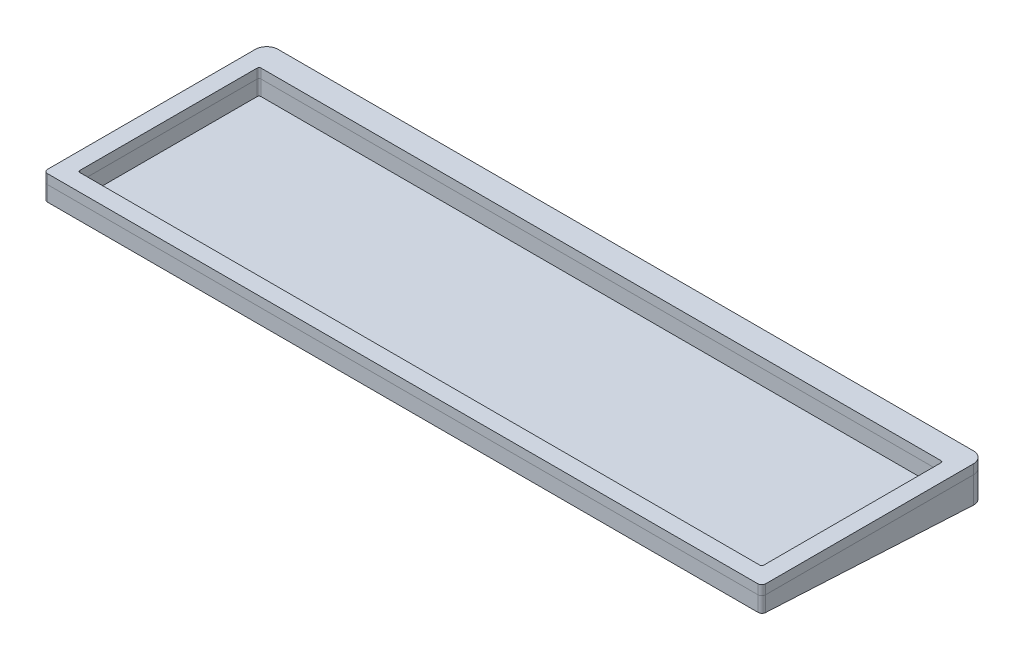
SolidWorks part; units mm, degrees
ref_plane "Front Plane" through (0, 0, 0) normal (0, 0, 1) x (1, 0, 0)
ref_plane "Top Plane" through (0, 0, 0) normal (0, 1, 0) x (1, 0, 0)
ref_plane "Right Plane" through (0, 0, 0) normal (1, 0, 0) x (0, 0, -1)
sketch "Sketch1" plane through (0, 0, 0) normal (0, 1, 0) x (1, 0, 0)
  line L1 (-178.825, 47.625) -> (178.825, 47.625)
  line L2 (-179.825, 46.625) -> (-179.825, -46.625)
  line L3 (-178.825, -47.625) -> (178.825, -47.625)
  line L4 (179.825, 46.625) -> (179.825, -46.625)
  line L5 (-179.825, 47.625) -> (179.825, -47.625) construction
  line L6 (-179.825, -47.625) -> (179.825, 47.625) construction
  arc A0 (178.825, -47.625) -> (179.825, -46.625) centre (178.825, -46.625) ccw
  arc A1 (178.825, 47.625) -> (179.825, 46.625) centre (178.825, 46.625) cw
  arc A2 (-179.825, -46.625) -> (-178.825, -47.625) centre (-178.825, -46.625) ccw
  arc A3 (-178.825, 47.625) -> (-179.825, 46.625) centre (-178.825, 46.625) ccw
  circle A4 centre (157.075, 19.175) radius 1.1
  circle A5 centre (136.925, -16.775) radius 1.1
  circle A6 centre (-153.475, 33.725) radius 1.1
  circle A7 centre (17.925, 22.275) radius 1.1
  circle A8 centre (17.875, -35.075) radius 1.1
  circle A9 centre (-130.375, -35.725) radius 1.1
  point P0 (0, 0)
  dimension "D3" = 1
  dimension "D4" = 2.2
  dimension "D7" = 2.2
  dimension "D8" = 2.2
  dimension "D9" = 2.2
  dimension "D10" = 2.2
  dimension "D11" = 2.2
  dimension "D1" = 359.65
  dimension "D2" = 95.25
  dimension "D5" = 22.75
  dimension "D6" = 28.45
  dimension "D12" = 42.9
  dimension "D13" = 30.85
  dimension "D14" = 25.35
  dimension "D15" = 161.9
  dimension "D16" = 12.55
  dimension "D17" = 161.95
  dimension "D18" = 11.9
  dimension "D19" = 49.45
  dimension "D20" = 13.9
  dimension "D21" = 26.35
sketch "Sketch2" plane through (0, 0, 0) normal (0, 1, 0) x (1, 0, 0)
  line L0 (-179.825, 46.625) -> (-179.825, -46.625) construction
  line L1 (-178.825, -47.625) -> (178.825, -47.625) construction
  line L2 (179.825, 46.625) -> (179.825, -46.625) construction
  line L3 (-178.825, 47.625) -> (178.825, 47.625) construction
  line L4 (-179.825, 46.625) -> (-179.825, -46.625)
  line L5 (-178.825, -47.625) -> (178.825, -47.625)
  line L6 (179.825, 46.625) -> (179.825, -46.625)
  line L7 (-178.825, 47.625) -> (178.825, 47.625)
  line L9 (-182.825, 60.625) -> (182.825, 60.625)
  line L10 (-188.825, 54.625) -> (-188.825, -54.625)
  line L11 (-186.825, -56.625) -> (186.825, -56.625)
  line L12 (188.825, 54.625) -> (188.825, -54.625)
  circle A0 centre (157.075, 19.175) radius 1.1 construction
  circle A1 centre (136.925, -16.775) radius 1.1 construction
  circle A2 centre (17.875, -35.075) radius 1.1 construction
  circle A3 centre (17.925, 22.275) radius 1.1 construction
  circle A4 centre (-153.475, 33.725) radius 1.1 construction
  circle A5 centre (-130.375, -35.725) radius 1.1 construction
  arc A6 (-179.825, -46.625) -> (-178.825, -47.625) centre (-178.825, -46.625) ccw construction
  arc A7 (178.825, -47.625) -> (179.825, -46.625) centre (178.825, -46.625) ccw construction
  arc A8 (179.825, 46.625) -> (178.825, 47.625) centre (178.825, 46.625) ccw construction
  arc A9 (-178.825, 47.625) -> (-179.825, 46.625) centre (-178.825, 46.625) ccw construction
  circle A10 centre (157.075, 19.175) radius 1.1
  circle A11 centre (136.925, -16.775) radius 1.1
  circle A12 centre (17.875, -35.075) radius 1.1
  circle A13 centre (17.925, 22.275) radius 1.1
  circle A14 centre (-153.475, 33.725) radius 1.1
  circle A15 centre (-130.375, -35.725) radius 1.1
  arc A16 (-179.825, -46.625) -> (-178.825, -47.625) centre (-178.825, -46.625) ccw
  arc A17 (178.825, -47.625) -> (179.825, -46.625) centre (178.825, -46.625) ccw
  arc A18 (179.825, 46.625) -> (178.825, 47.625) centre (178.825, 46.625) ccw
  arc A19 (-178.825, 47.625) -> (-179.825, 46.625) centre (-178.825, 46.625) ccw
  arc A20 (182.825, 60.625) -> (188.825, 54.625) centre (182.825, 54.625) cw
  arc A21 (-182.825, 60.625) -> (-188.825, 54.625) centre (-182.825, 54.625) ccw
  arc A22 (186.825, -56.625) -> (188.825, -54.625) centre (186.825, -54.625) ccw
  arc A23 (-188.825, -54.625) -> (-186.825, -56.625) centre (-186.825, -54.625) ccw
  point P30 (0, 0)
  dimension "D5" = 6
  dimension "D6" = 2
  dimension "D1" = 13
  dimension "D2" = 9
  dimension "D3" = 9
  dimension "D4" = 9
extrude "Boss-Extrude1" add sketch "Sketch2" along normal blind 13 contours L10 A23 L11 A22 L12 A20 L9 A21 A19 L7 A18 L6 A17 L5 A16 L4 region at (0, 0, -56.6707)
sketch "Sketch4" plane through (0, 0, 0) normal (0, -1, 0) x (1, 0, 0)
  line L0 (188.825, -54.625) -> (188.825, 54.625) construction
  line L1 (-182.825, -60.625) -> (182.825, -60.625) construction
  line L2 (-188.825, -54.625) -> (-188.825, 54.625) construction
  line L3 (-186.825, 56.625) -> (186.825, 56.625) construction
  line L4 (-179.825, 46.625) -> (-179.825, -46.625)
  line L5 (178.825, 47.625) -> (-178.825, 47.625)
  line L6 (179.825, -46.625) -> (179.825, 46.625)
  line L7 (-178.825, -47.625) -> (178.825, -47.625)
  line L8 (-179.825, 46.625) -> (-179.825, -46.625)
  line L10 (179.825, -46.625) -> (179.825, 46.625)
  line L11 (-178.825, -47.625) -> (178.825, -47.625)
  line L12 (188.825, -54.625) -> (188.825, 54.625)
  line L13 (-182.825, -60.625) -> (182.825, -60.625)
  line L14 (-188.825, -54.625) -> (-188.825, 54.625)
  line L15 (-186.825, 56.625) -> (186.825, 56.625)
  arc A0 (188.825, 54.625) -> (186.825, 56.625) centre (186.825, 54.625) ccw construction
  arc A1 (182.825, -60.625) -> (188.825, -54.625) centre (182.825, -54.625) ccw construction
  arc A2 (-188.825, -54.625) -> (-182.825, -60.625) centre (-182.825, -54.625) ccw construction
  arc A3 (-186.825, 56.625) -> (-188.825, 54.625) centre (-186.825, 54.625) ccw construction
  arc A4 (-179.825, -46.625) -> (-178.825, -47.625) centre (-178.825, -46.625) ccw
  arc A5 (-178.825, 47.625) -> (-179.825, 46.625) centre (-178.825, 46.625) ccw
  arc A6 (179.825, 46.625) -> (178.825, 47.625) centre (178.825, 46.625) ccw
  arc A7 (178.825, -47.625) -> (179.825, -46.625) centre (178.825, -46.625) ccw
  arc A8 (-179.825, -46.625) -> (-178.825, -47.625) centre (-178.825, -46.625) ccw
  arc A9 (-178.825, 47.625) -> (-179.825, 46.625) centre (-178.825, 46.625) ccw
  arc A10 (179.825, 46.625) -> (178.825, 47.625) centre (178.825, 46.625) ccw
  arc A11 (178.825, -47.625) -> (179.825, -46.625) centre (178.825, -46.625) ccw
  arc A12 (188.825, 54.625) -> (186.825, 56.625) centre (186.825, 54.625) ccw
  arc A13 (182.825, -60.625) -> (188.825, -54.625) centre (182.825, -54.625) ccw
  arc A14 (-188.825, -54.625) -> (-182.825, -60.625) centre (-182.825, -54.625) ccw
  arc A15 (-186.825, 56.625) -> (-188.825, 54.625) centre (-186.825, 54.625) ccw
  arc M9 (-178.825, -47.625) -> (-179.825, -46.625) centre (-178.825, -46.625) cw
  line M10 (-179.825, -46.625) -> (-179.825, 46.625)
  arc M11 (-179.825, 46.625) -> (-178.825, 47.625) centre (-178.825, 46.625) cw
  line M12 (-178.825, 47.625) -> (178.825, 47.625)
  arc M13 (178.825, 47.625) -> (179.825, 46.625) centre (178.825, 46.625) cw
  line M14 (179.825, 46.625) -> (179.825, -46.625)
  arc M15 (179.825, -46.625) -> (178.825, -47.625) centre (178.825, -46.625) cw
  line M16 (178.825, -47.625) -> (-178.825, -47.625)
  line M17 (-188.825, 54.625) -> (-188.825, -54.625)
  arc M18 (-188.825, -54.625) -> (-182.825, -60.625) centre (-182.825, -54.625) ccw
  line M19 (-182.825, -60.625) -> (182.825, -60.625)
  arc M20 (182.825, -60.625) -> (188.825, -54.625) centre (182.825, -54.625) ccw
  line M21 (188.825, -54.625) -> (188.825, 54.625)
  arc M22 (188.825, 54.625) -> (186.825, 56.625) centre (186.825, 54.625) ccw
  line M23 (186.825, 56.625) -> (-186.825, 56.625)
  arc M24 (-186.825, 56.625) -> (-188.825, 54.625) centre (-186.825, 54.625) ccw
  dimension "D1" = 0
extrude "Boss-Extrude3" add sketch "Sketch4" along normal blind 10.5 contours M24 M17 M18 M19 M20 M21 M22 M23 M16 M9 M10 M11 M12 M13 M14 M15 | M9 M16 M15 M14 M13 M12 M11 M10 region at (0, 0, 0) region at (184.2715, 0, -56.0715)
sketch "Sketch8" plane through (-188.825, 0, 0) normal (-1, 0, 0) x (0, 0, 1)
  line L0 (54.625, 0) -> (-57.625, 0) construction
  line L2 (-60.625, 13) -> (-60.625, -10.5) construction
  line L4 (-60.625, -6.1448) -> (-60.625, -10.5)
  line L5 (-60.625, -10.5) -> (56.625, -10.5)
  line L11 (56.625, 0) -> (56.625, -10.5)
  line L12 (56.625, 13) -> (56.625, -10.5) construction
  line L13 (-60.625, -6.1448) -> (56.625, 0)
  dimension "D1" = 2
  dimension "D2" = 10.5
  dimension "D3" = 87
extrude "Cut-Extrude4" cut sketch "Sketch8" against normal blind 400
sketch "Sketch9" plane through (0, 0, 0) normal (0, 1, 0) x (1, 0, 0)
  line L0 (-121.9453, 45.1) -> (-108.9453, 45.1)
  line L1 (-121.9453, 31.1) -> (-108.9453, 31.1)
  line L2 (-122.4453, 44.6) -> (-122.4453, 31.6)
  line L3 (-108.4453, 44.6) -> (-108.4453, 31.6)
  line L4 (-102.8953, 45.1) -> (-89.8953, 45.1)
  line L5 (-102.8953, 31.1) -> (-89.8953, 31.1)
  line L6 (-103.3953, 44.6) -> (-103.3953, 31.6)
  line L7 (-89.3953, 44.6) -> (-89.3953, 31.6)
  line L8 (-83.8453, 45.1) -> (-70.8453, 45.1)
  line L9 (-83.8453, 31.1) -> (-70.8453, 31.1)
  line L10 (-84.3453, 44.6) -> (-84.3453, 31.6)
  line L11 (-70.3453, 44.6) -> (-70.3453, 31.6)
  line L12 (-64.7953, 45.1) -> (-51.7953, 45.1)
  line L13 (-64.7953, 31.1) -> (-51.7953, 31.1)
  line L14 (-65.2953, 44.6) -> (-65.2953, 31.6)
  line L15 (-51.2953, 44.6) -> (-51.2953, 31.6)
  line L16 (-45.7453, 45.1) -> (-32.7453, 45.1)
  line L17 (-45.7453, 31.1) -> (-32.7453, 31.1)
  line L18 (-46.2453, 44.6) -> (-46.2453, 31.6)
  line L19 (-32.2453, 44.6) -> (-32.2453, 31.6)
  line L20 (-26.6953, 45.1) -> (-13.6953, 45.1)
  line L21 (-26.6953, 31.1) -> (-13.6953, 31.1)
  line L22 (-27.1953, 44.6) -> (-27.1953, 31.6)
  line L23 (-13.1953, 44.6) -> (-13.1953, 31.6)
  line L24 (-7.6453, 45.1) -> (5.3547, 45.1)
  line L25 (-7.6453, 31.1) -> (5.3547, 31.1)
  line L26 (-8.1453, 44.6) -> (-8.1453, 31.6)
  line L27 (5.8547, 44.6) -> (5.8547, 31.6)
  line L28 (11.4047, 45.1) -> (24.4047, 45.1)
  line L29 (11.4047, 31.1) -> (24.4047, 31.1)
  line L30 (10.9047, 44.6) -> (10.9047, 31.6)
  line L31 (24.9047, 44.6) -> (24.9047, 31.6)
  line L32 (30.4547, 45.1) -> (43.4547, 45.1)
  line L33 (30.4547, 31.1) -> (43.4547, 31.1)
  line L34 (29.9547, 44.6) -> (29.9547, 31.6)
  line L35 (43.9547, 44.6) -> (43.9547, 31.6)
  line L36 (49.5047, 45.1) -> (62.5047, 45.1)
  line L37 (49.5047, 31.1) -> (62.5047, 31.1)
  line L38 (49.0047, 44.6) -> (49.0047, 31.6)
  line L39 (63.0047, 44.6) -> (63.0047, 31.6)
  line L40 (68.5547, 45.1) -> (81.5547, 45.1)
  line L41 (68.5547, 31.1) -> (81.5547, 31.1)
  line L42 (68.0547, 44.6) -> (68.0547, 31.6)
  line L43 (82.0547, 44.6) -> (82.0547, 31.6)
  line L44 (87.6047, 45.1) -> (100.6047, 45.1)
  line L45 (87.6047, 31.1) -> (100.6047, 31.1)
  line L46 (87.1047, 44.6) -> (87.1047, 31.6)
  line L47 (101.1047, 44.6) -> (101.1047, 31.6)
  line L48 (106.6547, 45.1) -> (119.6547, 45.1)
  line L49 (106.6547, 31.1) -> (119.6547, 31.1)
  line L50 (106.1547, 44.6) -> (106.1547, 31.6)
  line L51 (120.1547, 44.6) -> (120.1547, 31.6)
  line L52 (135.2297, 45.1) -> (148.2297, 45.1)
  line L53 (135.2297, 31.1) -> (148.2297, 31.1)
  line L54 (134.7297, 44.6) -> (134.7297, 31.6)
  line L55 (148.7297, 44.6) -> (148.7297, 31.6)
  line L56 (150.6677, 44.1) -> (156.6677, 44.1)
  line L57 (150.6677, 29.1) -> (156.6677, 29.1)
  line L58 (150.1677, 43.6) -> (150.1677, 29.6)
  line L59 (157.1677, 43.6) -> (157.1677, 29.6)
  line L60 (126.7917, 44.1) -> (132.7917, 44.1)
  line L61 (126.7917, 29.1) -> (132.7917, 29.1)
  line L62 (126.2917, 43.6) -> (126.2917, 29.6)
  line L63 (133.2917, 43.6) -> (133.2917, 29.6)
  line L64 (163.8047, 45.1) -> (176.8047, 45.1)
  line L65 (163.8047, 31.1) -> (176.8047, 31.1)
  line L66 (163.3047, 44.6) -> (163.3047, 31.6)
  line L67 (177.3047, 44.6) -> (177.3047, 31.6)
  line L68 (-117.1828, 26.05) -> (-104.1828, 26.05)
  line L69 (-117.1828, 12.05) -> (-104.1828, 12.05)
  line L70 (-117.6828, 25.55) -> (-117.6828, 12.55)
  line L71 (-103.6828, 25.55) -> (-103.6828, 12.55)
  line L72 (-93.3703, 26.05) -> (-80.3703, 26.05)
  line L73 (-93.3703, 12.05) -> (-80.3703, 12.05)
  line L74 (-93.8703, 25.55) -> (-93.8703, 12.55)
  line L75 (-79.8703, 25.55) -> (-79.8703, 12.55)
  line L76 (-74.3203, 26.05) -> (-61.3203, 26.05)
  line L77 (-74.3203, 12.05) -> (-61.3203, 12.05)
  line L78 (-74.8203, 25.55) -> (-74.8203, 12.55)
  line L79 (-60.8203, 25.55) -> (-60.8203, 12.55)
  line L80 (-55.2703, 26.05) -> (-42.2703, 26.05)
  line L81 (-55.2703, 12.05) -> (-42.2703, 12.05)
  line L82 (-55.7703, 25.55) -> (-55.7703, 12.55)
  line L83 (-41.7703, 25.55) -> (-41.7703, 12.55)
  line L84 (-36.2203, 26.05) -> (-23.2203, 26.05)
  line L85 (-36.2203, 12.05) -> (-23.2203, 12.05)
  line L86 (-36.7203, 25.55) -> (-36.7203, 12.55)
  line L87 (-22.7203, 25.55) -> (-22.7203, 12.55)
  line L88 (-17.1703, 26.05) -> (-4.1703, 26.05)
  line L89 (-17.1703, 12.05) -> (-4.1703, 12.05)
  line L90 (-17.6703, 25.55) -> (-17.6703, 12.55)
  line L91 (-3.6703, 25.55) -> (-3.6703, 12.55)
  line L92 (1.8797, 26.05) -> (14.8797, 26.05)
  line L93 (1.8797, 12.05) -> (14.8797, 12.05)
  line L94 (1.3797, 25.55) -> (1.3797, 12.55)
  line L95 (15.3797, 25.55) -> (15.3797, 12.55)
  line L96 (20.9297, 26.05) -> (33.9297, 26.05)
  line L97 (20.9297, 12.05) -> (33.9297, 12.05)
  line L98 (20.4297, 25.55) -> (20.4297, 12.55)
  line L99 (34.4297, 25.55) -> (34.4297, 12.55)
  line L100 (39.9797, 26.05) -> (52.9797, 26.05)
  line L101 (39.9797, 12.05) -> (52.9797, 12.05)
  line L102 (39.4797, 25.55) -> (39.4797, 12.55)
  line L103 (53.4797, 25.55) -> (53.4797, 12.55)
  line L104 (59.0297, 26.05) -> (72.0297, 26.05)
  line L105 (59.0297, 12.05) -> (72.0297, 12.05)
  line L106 (58.5297, 25.55) -> (58.5297, 12.55)
  line L107 (72.5297, 25.55) -> (72.5297, 12.55)
  line L108 (78.0797, 26.05) -> (91.0797, 26.05)
  line L109 (78.0797, 12.05) -> (91.0797, 12.05)
  line L110 (77.5797, 25.55) -> (77.5797, 12.55)
  line L111 (91.5797, 25.55) -> (91.5797, 12.55)
  line L112 (97.1297, 26.05) -> (110.1297, 26.05)
  line L113 (97.1297, 12.05) -> (110.1297, 12.05)
  line L114 (96.6297, 25.55) -> (96.6297, 12.55)
  line L115 (110.6297, 25.55) -> (110.6297, 12.55)
  line L116 (116.1797, 26.05) -> (129.1797, 26.05)
  line L117 (116.1797, 12.05) -> (129.1797, 12.05)
  line L118 (115.6797, 25.55) -> (115.6797, 12.55)
  line L119 (129.6797, 25.55) -> (129.6797, 12.55)
  line L120 (139.9922, 26.05) -> (152.9922, 26.05)
  line L121 (139.9922, 12.05) -> (152.9922, 12.05)
  line L122 (139.4922, 25.55) -> (139.4922, 12.55)
  line L123 (153.4922, 25.55) -> (153.4922, 12.55)
  line L124 (163.8047, 26.05) -> (176.8047, 26.05)
  line L125 (163.8047, 12.05) -> (176.8047, 12.05)
  line L126 (163.3047, 25.55) -> (163.3047, 12.55)
  line L127 (177.3047, 25.55) -> (177.3047, 12.55)
  line L128 (-114.8016, 7) -> (-101.8016, 7)
  line L129 (-114.8016, -7) -> (-101.8016, -7)
  line L130 (-115.3016, 6.5) -> (-115.3016, -6.5)
  line L131 (-101.3016, 6.5) -> (-101.3016, -6.5)
  line L132 (-88.6078, 7) -> (-75.6078, 7)
  line L133 (-88.6078, -7) -> (-75.6078, -7)
  line L134 (-89.1078, 6.5) -> (-89.1078, -6.5)
  line L135 (-75.1078, 6.5) -> (-75.1078, -6.5)
  line L136 (-69.5578, 7) -> (-56.5578, 7)
  line L137 (-69.5578, -7) -> (-56.5578, -7)
  line L138 (-70.0578, 6.5) -> (-70.0578, -6.5)
  line L139 (-56.0578, 6.5) -> (-56.0578, -6.5)
  line L140 (-50.5078, 7) -> (-37.5078, 7)
  line L141 (-50.5078, -7) -> (-37.5078, -7)
  line L142 (-51.0078, 6.5) -> (-51.0078, -6.5)
  line L143 (-37.0078, 6.5) -> (-37.0078, -6.5)
  line L144 (-31.4578, 7) -> (-18.4578, 7)
  line L145 (-31.4578, -7) -> (-18.4578, -7)
  line L146 (-31.9578, 6.5) -> (-31.9578, -6.5)
  line L147 (-17.9578, 6.5) -> (-17.9578, -6.5)
  line L148 (-12.4078, 7) -> (0.5922, 7)
  line L149 (-12.4078, -7) -> (0.5922, -7)
  line L150 (-12.9078, 6.5) -> (-12.9078, -6.5)
  line L151 (1.0922, 6.5) -> (1.0922, -6.5)
  line L152 (6.6422, 7) -> (19.6422, 7)
  line L153 (6.6422, -7) -> (19.6422, -7)
  line L154 (6.1422, 6.5) -> (6.1422, -6.5)
  line L155 (20.1422, 6.5) -> (20.1422, -6.5)
  line L156 (25.6922, 7) -> (38.6922, 7)
  line L157 (25.6922, -7) -> (38.6922, -7)
  line L158 (25.1922, 6.5) -> (25.1922, -6.5)
  line L159 (39.1922, 6.5) -> (39.1922, -6.5)
  line L160 (44.7422, 7) -> (57.7422, 7)
  line L161 (44.7422, -7) -> (57.7422, -7)
  line L162 (44.2422, 6.5) -> (44.2422, -6.5)
  line L163 (58.2422, 6.5) -> (58.2422, -6.5)
  line L164 (63.7922, 7) -> (76.7922, 7)
  line L165 (63.7922, -7) -> (76.7922, -7)
  line L166 (63.2922, 6.5) -> (63.2922, -6.5)
  line L167 (77.2922, 6.5) -> (77.2922, -6.5)
  line L168 (82.8422, 7) -> (95.8422, 7)
  line L169 (82.8422, -7) -> (95.8422, -7)
  line L170 (82.3422, 6.5) -> (82.3422, -6.5)
  line L171 (96.3422, 6.5) -> (96.3422, -6.5)
  line L172 (101.8922, 7) -> (114.8922, 7)
  line L173 (101.8922, -7) -> (114.8922, -7)
  line L174 (101.3922, 6.5) -> (101.3922, -6.5)
  line L175 (115.3922, 6.5) -> (115.3922, -6.5)
  line L176 (132.8484, 7) -> (145.8484, 7)
  line L177 (132.8484, -7) -> (145.8484, -7)
  line L178 (132.3484, 6.5) -> (132.3484, -6.5)
  line L179 (146.3484, 6.5) -> (146.3484, -6.5)
  line L180 (148.2864, 6) -> (154.2864, 6)
  line L181 (148.2864, -9) -> (154.2864, -9)
  line L182 (147.7864, 5.5) -> (147.7864, -8.5)
  line L183 (154.7864, 5.5) -> (154.7864, -8.5)
  line L184 (124.4104, 6) -> (130.4104, 6)
  line L185 (124.4104, -9) -> (130.4104, -9)
  line L186 (123.9104, 5.5) -> (123.9104, -8.5)
  line L187 (130.9104, 5.5) -> (130.9104, -8.5)
  line L188 (163.8047, 7) -> (176.8047, 7)
  line L189 (163.8047, -7) -> (176.8047, -7)
  line L190 (163.3047, 6.5) -> (163.3047, -6.5)
  line L191 (177.3047, 6.5) -> (177.3047, -6.5)
  line L192 (-110.0391, -12.05) -> (-97.0391, -12.05)
  line L193 (-110.0391, -26.05) -> (-97.0391, -26.05)
  line L194 (-110.5391, -12.55) -> (-110.5391, -25.55)
  line L195 (-96.5391, -12.55) -> (-96.5391, -25.55)
  line L196 (-94.6011, -13.05) -> (-88.6011, -13.05)
  line L197 (-94.6011, -28.05) -> (-88.6011, -28.05)
  line L198 (-95.1011, -13.55) -> (-95.1011, -27.55)
  line L199 (-88.1011, -13.55) -> (-88.1011, -27.55)
  line L200 (-118.4771, -13.05) -> (-112.4771, -13.05)
  line L201 (-118.4771, -28.05) -> (-112.4771, -28.05)
  line L202 (-118.9771, -13.55) -> (-118.9771, -27.55)
  line L203 (-111.9771, -13.55) -> (-111.9771, -27.55)
  line L204 (-79.0828, -12.05) -> (-66.0828, -12.05)
  line L205 (-79.0828, -26.05) -> (-66.0828, -26.05)
  line L206 (-79.5828, -12.55) -> (-79.5828, -25.55)
  line L207 (-65.5828, -12.55) -> (-65.5828, -25.55)
  line L208 (-60.0328, -12.05) -> (-47.0328, -12.05)
  line L209 (-60.0328, -26.05) -> (-47.0328, -26.05)
  line L210 (-60.5328, -12.55) -> (-60.5328, -25.55)
  line L211 (-46.5328, -12.55) -> (-46.5328, -25.55)
  line L212 (-40.9828, -12.05) -> (-27.9828, -12.05)
  line L213 (-40.9828, -26.05) -> (-27.9828, -26.05)
  line L214 (-41.4828, -12.55) -> (-41.4828, -25.55)
  line L215 (-27.4828, -12.55) -> (-27.4828, -25.55)
  line L216 (-21.9328, -12.05) -> (-8.9328, -12.05)
  line L217 (-21.9328, -26.05) -> (-8.9328, -26.05)
  line L218 (-22.4328, -12.55) -> (-22.4328, -25.55)
  line L219 (-8.4328, -12.55) -> (-8.4328, -25.55)
  line L220 (-2.8828, -12.05) -> (10.1172, -12.05)
  line L221 (-2.8828, -26.05) -> (10.1172, -26.05)
  line L222 (-3.3828, -12.55) -> (-3.3828, -25.55)
  line L223 (10.6172, -12.55) -> (10.6172, -25.55)
  line L224 (16.1672, -12.05) -> (29.1672, -12.05)
  line L225 (16.1672, -26.05) -> (29.1672, -26.05)
  line L226 (15.6672, -12.55) -> (15.6672, -25.55)
  line L227 (29.6672, -12.55) -> (29.6672, -25.55)
  line L228 (35.2172, -12.05) -> (48.2172, -12.05)
  line L229 (35.2172, -26.05) -> (48.2172, -26.05)
  line L230 (34.7172, -12.55) -> (34.7172, -25.55)
  line L231 (48.7172, -12.55) -> (48.7172, -25.55)
  line L232 (54.2672, -12.05) -> (67.2672, -12.05)
  line L233 (54.2672, -26.05) -> (67.2672, -26.05)
  line L234 (53.7672, -12.55) -> (53.7672, -25.55)
  line L235 (67.7672, -12.55) -> (67.7672, -25.55)
  line L236 (73.3172, -12.05) -> (86.3172, -12.05)
  line L237 (73.3172, -26.05) -> (86.3172, -26.05)
  line L238 (72.8172, -12.55) -> (72.8172, -25.55)
  line L239 (86.8172, -12.55) -> (86.8172, -25.55)
  line L240 (92.3672, -12.05) -> (105.3672, -12.05)
  line L241 (92.3672, -26.05) -> (105.3672, -26.05)
  line L242 (91.8672, -12.55) -> (91.8672, -25.55)
  line L243 (105.8672, -12.55) -> (105.8672, -25.55)
  line L244 (118.5609, -12.05) -> (131.5609, -12.05)
  line L245 (118.5609, -26.05) -> (131.5609, -26.05)
  line L246 (118.0609, -12.55) -> (118.0609, -25.55)
  line L247 (132.0609, -12.55) -> (132.0609, -25.55)
  line L248 (144.7547, -12.05) -> (157.7547, -12.05)
  line L249 (144.7547, -26.05) -> (157.7547, -26.05)
  line L250 (144.2547, -12.55) -> (144.2547, -25.55)
  line L251 (158.2547, -12.55) -> (158.2547, -25.55)
  line L252 (163.8047, -12.05) -> (176.8047, -12.05)
  line L253 (163.8047, -26.05) -> (176.8047, -26.05)
  line L254 (163.3047, -12.55) -> (163.3047, -25.55)
  line L255 (177.3047, -12.55) -> (177.3047, -25.55)
  line L256 (-119.5641, -31.1) -> (-106.5641, -31.1)
  line L257 (-119.5641, -45.1) -> (-106.5641, -45.1)
  line L258 (-120.0641, -31.6) -> (-120.0641, -44.6)
  line L259 (-106.0641, -31.6) -> (-106.0641, -44.6)
  line L260 (-95.7516, -31.1) -> (-82.7516, -31.1)
  line L261 (-95.7516, -45.1) -> (-82.7516, -45.1)
  line L262 (-96.2516, -31.6) -> (-96.2516, -44.6)
  line L263 (-82.2516, -31.6) -> (-82.2516, -44.6)
  line L264 (-71.9391, -31.1) -> (-58.9391, -31.1)
  line L265 (-71.9391, -45.1) -> (-58.9391, -45.1)
  line L266 (-72.4391, -31.6) -> (-72.4391, -44.6)
  line L267 (-58.4391, -31.6) -> (-58.4391, -44.6)
  line L268 (-0.5016, -31.1) -> (12.4984, -31.1)
  line L269 (-0.5016, -45.1) -> (12.4984, -45.1)
  line L270 (-1.0016, -31.6) -> (-1.0016, -44.6)
  line L271 (12.9984, -31.6) -> (12.9984, -44.6)
  line L272 (52.9984, -32.1) -> (58.9984, -32.1)
  line L273 (52.9984, -47.1) -> (58.9984, -47.1)
  line L274 (52.4984, -32.6) -> (52.4984, -46.6)
  line L275 (59.4984, -32.6) -> (59.4984, -46.6)
  line L276 (-47.0016, -32.1) -> (-41.0016, -32.1)
  line L277 (-47.0016, -47.1) -> (-41.0016, -47.1)
  line L278 (-47.5016, -32.6) -> (-47.5016, -46.6)
  line L279 (-40.5016, -32.6) -> (-40.5016, -46.6)
  line L280 (68.5547, -31.1) -> (81.5547, -31.1)
  line L281 (68.5547, -45.1) -> (81.5547, -45.1)
  line L282 (68.0547, -31.6) -> (68.0547, -44.6)
  line L283 (82.0547, -31.6) -> (82.0547, -44.6)
  line L284 (87.6047, -31.1) -> (100.6047, -31.1)
  line L285 (87.6047, -45.1) -> (100.6047, -45.1)
  line L286 (87.1047, -31.6) -> (87.1047, -44.6)
  line L287 (101.1047, -31.6) -> (101.1047, -44.6)
  line L288 (106.6547, -31.1) -> (119.6547, -31.1)
  line L289 (106.6547, -45.1) -> (119.6547, -45.1)
  line L290 (106.1547, -31.6) -> (106.1547, -44.6)
  line L291 (120.1547, -31.6) -> (120.1547, -44.6)
  line L292 (125.7047, -31.1) -> (138.7047, -31.1)
  line L293 (125.7047, -45.1) -> (138.7047, -45.1)
  line L294 (125.2047, -31.6) -> (125.2047, -44.6)
  line L295 (139.2047, -31.6) -> (139.2047, -44.6)
  line L296 (144.7547, -31.1) -> (157.7547, -31.1)
  line L297 (144.7547, -45.1) -> (157.7547, -45.1)
  line L298 (144.2547, -31.6) -> (144.2547, -44.6)
  line L299 (158.2547, -31.6) -> (158.2547, -44.6)
  line L300 (163.8047, -31.1) -> (176.8047, -31.1)
  line L301 (163.8047, -45.1) -> (176.8047, -45.1)
  line L302 (163.3047, -31.6) -> (163.3047, -44.6)
  line L303 (177.3047, -31.6) -> (177.3047, -44.6)
  line L304 (-122.9703, 47.625) -> (-103.2456, 47.625)
  line L305 (-122.9703, -47.625) -> (-103.2456, -47.625)
  line L306 (-124.9703, 45.625) -> (-124.9703, -45.625)
  line L307 (179.8297, 45.625) -> (179.8297, 7.5)
  line L308 (-103.2456, 53.125) -> (-103.2456, 47.625)
  line L309 (-124.9703, 47.625) -> (-103.2456, 47.625)
  line L311 (-101.2456, 55.125) -> (-90.2456, 55.125)
  line L312 (-88.2456, 47.625) -> (-88.2456, 53.125)
  line L313 (-23.2456, 53.125) -> (-23.2456, 47.625)
  line L314 (-21.2456, 55.125) -> (-10.2456, 55.125)
  line L315 (-8.2456, 47.625) -> (-8.2456, 53.125)
  line L316 (56.7544, 53.125) -> (56.7544, 47.625)
  line L317 (58.7544, 55.125) -> (69.7544, 55.125)
  line L318 (71.7544, 47.625) -> (71.7544, 53.125)
  line L319 (136.7544, 53.125) -> (136.7544, 47.625)
  line L320 (138.7544, 55.125) -> (149.7544, 55.125)
  line L321 (151.7544, 47.625) -> (151.7544, 53.125)
  line L322 (-88.2456, 47.625) -> (-23.2456, 47.625)
  line L323 (-8.2456, 47.625) -> (56.7544, 47.625)
  line L324 (71.7544, 47.625) -> (136.7544, 47.625)
  line L325 (151.7544, 47.625) -> (177.8297, 47.625)
  line L326 (-23.2456, -47.625) -> (-23.2456, -52.625)
  line L327 (-5.699, -47.625) -> (-5.699, -52.625)
  line L329 (-103.2456, -47.625) -> (-103.2456, -52.625)
  line L330 (-101.2456, -54.625) -> (-87.699, -54.625)
  line L331 (-85.699, -47.625) -> (-85.699, -52.625)
  line L332 (-21.2456, -54.625) -> (-7.699, -54.625)
  line L333 (56.7544, -47.625) -> (56.7544, -52.625)
  line L334 (74.301, -47.625) -> (74.301, -52.625)
  line L335 (58.7544, -54.625) -> (72.301, -54.625)
  line L336 (136.7544, -47.625) -> (136.7544, -52.625)
  line L337 (154.301, -47.625) -> (154.301, -52.625)
  line L338 (138.7544, -54.625) -> (152.301, -54.625)
  line L339 (-85.699, -47.625) -> (-23.2456, -47.625)
  line L340 (-5.699, -47.625) -> (56.7544, -47.625)
  line L341 (74.301, -47.625) -> (136.7544, -47.625)
  line L342 (154.301, -47.625) -> (177.8297, -47.625)
  line L343 (179.8297, -7.5) -> (179.8297, -45.625)
  line L344 (179.8297, 7.5) -> (184.9092, 7.5)
  line L346 (179.8297, -7.5) -> (184.9092, -7.5)
  line L347 (186.9092, 5.5) -> (186.9092, -5.5)
  arc A0 (-121.9453, 45.1) -> (-122.4453, 44.6) centre (-121.9453, 44.6) ccw
  arc A1 (-108.4453, 44.6) -> (-108.9453, 45.1) centre (-108.9453, 44.6) ccw
  arc A2 (-122.4453, 31.6) -> (-121.9453, 31.1) centre (-121.9453, 31.6) ccw
  arc A3 (-108.9453, 31.1) -> (-108.4453, 31.6) centre (-108.9453, 31.6) ccw
  arc A4 (-102.8953, 45.1) -> (-103.3953, 44.6) centre (-102.8953, 44.6) ccw
  arc A5 (-89.3953, 44.6) -> (-89.8953, 45.1) centre (-89.8953, 44.6) ccw
  arc A6 (-103.3953, 31.6) -> (-102.8953, 31.1) centre (-102.8953, 31.6) ccw
  arc A7 (-89.8953, 31.1) -> (-89.3953, 31.6) centre (-89.8953, 31.6) ccw
  arc A8 (-83.8453, 45.1) -> (-84.3453, 44.6) centre (-83.8453, 44.6) ccw
  arc A9 (-70.3453, 44.6) -> (-70.8453, 45.1) centre (-70.8453, 44.6) ccw
  arc A10 (-84.3453, 31.6) -> (-83.8453, 31.1) centre (-83.8453, 31.6) ccw
  arc A11 (-70.8453, 31.1) -> (-70.3453, 31.6) centre (-70.8453, 31.6) ccw
  arc A12 (-64.7953, 45.1) -> (-65.2953, 44.6) centre (-64.7953, 44.6) ccw
  arc A13 (-51.2953, 44.6) -> (-51.7953, 45.1) centre (-51.7953, 44.6) ccw
  arc A14 (-65.2953, 31.6) -> (-64.7953, 31.1) centre (-64.7953, 31.6) ccw
  arc A15 (-51.7953, 31.1) -> (-51.2953, 31.6) centre (-51.7953, 31.6) ccw
  arc A16 (-45.7453, 45.1) -> (-46.2453, 44.6) centre (-45.7453, 44.6) ccw
  arc A17 (-32.2453, 44.6) -> (-32.7453, 45.1) centre (-32.7453, 44.6) ccw
  arc A18 (-46.2453, 31.6) -> (-45.7453, 31.1) centre (-45.7453, 31.6) ccw
  arc A19 (-32.7453, 31.1) -> (-32.2453, 31.6) centre (-32.7453, 31.6) ccw
  arc A20 (-26.6953, 45.1) -> (-27.1953, 44.6) centre (-26.6953, 44.6) ccw
  arc A21 (-13.1953, 44.6) -> (-13.6953, 45.1) centre (-13.6953, 44.6) ccw
  arc A22 (-27.1953, 31.6) -> (-26.6953, 31.1) centre (-26.6953, 31.6) ccw
  arc A23 (-13.6953, 31.1) -> (-13.1953, 31.6) centre (-13.6953, 31.6) ccw
  arc A24 (-7.6453, 45.1) -> (-8.1453, 44.6) centre (-7.6453, 44.6) ccw
  arc A25 (5.8547, 44.6) -> (5.3547, 45.1) centre (5.3547, 44.6) ccw
  arc A26 (-8.1453, 31.6) -> (-7.6453, 31.1) centre (-7.6453, 31.6) ccw
  arc A27 (5.3547, 31.1) -> (5.8547, 31.6) centre (5.3547, 31.6) ccw
  arc A28 (11.4047, 45.1) -> (10.9047, 44.6) centre (11.4047, 44.6) ccw
  arc A29 (24.9047, 44.6) -> (24.4047, 45.1) centre (24.4047, 44.6) ccw
  arc A30 (10.9047, 31.6) -> (11.4047, 31.1) centre (11.4047, 31.6) ccw
  arc A31 (24.4047, 31.1) -> (24.9047, 31.6) centre (24.4047, 31.6) ccw
  arc A32 (30.4547, 45.1) -> (29.9547, 44.6) centre (30.4547, 44.6) ccw
  arc A33 (43.9547, 44.6) -> (43.4547, 45.1) centre (43.4547, 44.6) ccw
  arc A34 (29.9547, 31.6) -> (30.4547, 31.1) centre (30.4547, 31.6) ccw
  arc A35 (43.4547, 31.1) -> (43.9547, 31.6) centre (43.4547, 31.6) ccw
  arc A36 (49.5047, 45.1) -> (49.0047, 44.6) centre (49.5047, 44.6) ccw
  arc A37 (63.0047, 44.6) -> (62.5047, 45.1) centre (62.5047, 44.6) ccw
  arc A38 (49.0047, 31.6) -> (49.5047, 31.1) centre (49.5047, 31.6) ccw
  arc A39 (62.5047, 31.1) -> (63.0047, 31.6) centre (62.5047, 31.6) ccw
  arc A40 (68.5547, 45.1) -> (68.0547, 44.6) centre (68.5547, 44.6) ccw
  arc A41 (82.0547, 44.6) -> (81.5547, 45.1) centre (81.5547, 44.6) ccw
  arc A42 (68.0547, 31.6) -> (68.5547, 31.1) centre (68.5547, 31.6) ccw
  arc A43 (81.5547, 31.1) -> (82.0547, 31.6) centre (81.5547, 31.6) ccw
  arc A44 (87.6047, 45.1) -> (87.1047, 44.6) centre (87.6047, 44.6) ccw
  arc A45 (101.1047, 44.6) -> (100.6047, 45.1) centre (100.6047, 44.6) ccw
  arc A46 (87.1047, 31.6) -> (87.6047, 31.1) centre (87.6047, 31.6) ccw
  arc A47 (100.6047, 31.1) -> (101.1047, 31.6) centre (100.6047, 31.6) ccw
  arc A48 (106.6547, 45.1) -> (106.1547, 44.6) centre (106.6547, 44.6) ccw
  arc A49 (120.1547, 44.6) -> (119.6547, 45.1) centre (119.6547, 44.6) ccw
  arc A50 (106.1547, 31.6) -> (106.6547, 31.1) centre (106.6547, 31.6) ccw
  arc A51 (119.6547, 31.1) -> (120.1547, 31.6) centre (119.6547, 31.6) ccw
  arc A52 (135.2297, 45.1) -> (134.7297, 44.6) centre (135.2297, 44.6) ccw
  arc A53 (148.7297, 44.6) -> (148.2297, 45.1) centre (148.2297, 44.6) ccw
  arc A54 (134.7297, 31.6) -> (135.2297, 31.1) centre (135.2297, 31.6) ccw
  arc A55 (148.2297, 31.1) -> (148.7297, 31.6) centre (148.2297, 31.6) ccw
  arc A56 (150.6677, 44.1) -> (150.1677, 43.6) centre (150.6677, 43.6) ccw
  arc A57 (157.1677, 43.6) -> (156.6677, 44.1) centre (156.6677, 43.6) ccw
  arc A58 (150.1677, 29.6) -> (150.6677, 29.1) centre (150.6677, 29.6) ccw
  arc A59 (156.6677, 29.1) -> (157.1677, 29.6) centre (156.6677, 29.6) ccw
  arc A60 (126.7917, 44.1) -> (126.2917, 43.6) centre (126.7917, 43.6) ccw
  arc A61 (133.2917, 43.6) -> (132.7917, 44.1) centre (132.7917, 43.6) ccw
  arc A62 (126.2917, 29.6) -> (126.7917, 29.1) centre (126.7917, 29.6) ccw
  arc A63 (132.7917, 29.1) -> (133.2917, 29.6) centre (132.7917, 29.6) ccw
  arc A64 (163.8047, 45.1) -> (163.3047, 44.6) centre (163.8047, 44.6) ccw
  arc A65 (177.3047, 44.6) -> (176.8047, 45.1) centre (176.8047, 44.6) ccw
  arc A66 (163.3047, 31.6) -> (163.8047, 31.1) centre (163.8047, 31.6) ccw
  arc A67 (176.8047, 31.1) -> (177.3047, 31.6) centre (176.8047, 31.6) ccw
  arc A68 (-117.1828, 26.05) -> (-117.6828, 25.55) centre (-117.1828, 25.55) ccw
  arc A69 (-103.6828, 25.55) -> (-104.1828, 26.05) centre (-104.1828, 25.55) ccw
  arc A70 (-117.6828, 12.55) -> (-117.1828, 12.05) centre (-117.1828, 12.55) ccw
  arc A71 (-104.1828, 12.05) -> (-103.6828, 12.55) centre (-104.1828, 12.55) ccw
  arc A72 (-93.3703, 26.05) -> (-93.8703, 25.55) centre (-93.3703, 25.55) ccw
  arc A73 (-79.8703, 25.55) -> (-80.3703, 26.05) centre (-80.3703, 25.55) ccw
  arc A74 (-93.8703, 12.55) -> (-93.3703, 12.05) centre (-93.3703, 12.55) ccw
  arc A75 (-80.3703, 12.05) -> (-79.8703, 12.55) centre (-80.3703, 12.55) ccw
  arc A76 (-74.3203, 26.05) -> (-74.8203, 25.55) centre (-74.3203, 25.55) ccw
  arc A77 (-60.8203, 25.55) -> (-61.3203, 26.05) centre (-61.3203, 25.55) ccw
  arc A78 (-74.8203, 12.55) -> (-74.3203, 12.05) centre (-74.3203, 12.55) ccw
  arc A79 (-61.3203, 12.05) -> (-60.8203, 12.55) centre (-61.3203, 12.55) ccw
  arc A80 (-55.2703, 26.05) -> (-55.7703, 25.55) centre (-55.2703, 25.55) ccw
  arc A81 (-41.7703, 25.55) -> (-42.2703, 26.05) centre (-42.2703, 25.55) ccw
  arc A82 (-55.7703, 12.55) -> (-55.2703, 12.05) centre (-55.2703, 12.55) ccw
  arc A83 (-42.2703, 12.05) -> (-41.7703, 12.55) centre (-42.2703, 12.55) ccw
  arc A84 (-36.2203, 26.05) -> (-36.7203, 25.55) centre (-36.2203, 25.55) ccw
  arc A85 (-22.7203, 25.55) -> (-23.2203, 26.05) centre (-23.2203, 25.55) ccw
  arc A86 (-36.7203, 12.55) -> (-36.2203, 12.05) centre (-36.2203, 12.55) ccw
  arc A87 (-23.2203, 12.05) -> (-22.7203, 12.55) centre (-23.2203, 12.55) ccw
  arc A88 (-17.1703, 26.05) -> (-17.6703, 25.55) centre (-17.1703, 25.55) ccw
  arc A89 (-3.6703, 25.55) -> (-4.1703, 26.05) centre (-4.1703, 25.55) ccw
  arc A90 (-17.6703, 12.55) -> (-17.1703, 12.05) centre (-17.1703, 12.55) ccw
  arc A91 (-4.1703, 12.05) -> (-3.6703, 12.55) centre (-4.1703, 12.55) ccw
  arc A92 (1.8797, 26.05) -> (1.3797, 25.55) centre (1.8797, 25.55) ccw
  arc A93 (15.3797, 25.55) -> (14.8797, 26.05) centre (14.8797, 25.55) ccw
  arc A94 (1.3797, 12.55) -> (1.8797, 12.05) centre (1.8797, 12.55) ccw
  arc A95 (14.8797, 12.05) -> (15.3797, 12.55) centre (14.8797, 12.55) ccw
  arc A96 (20.9297, 26.05) -> (20.4297, 25.55) centre (20.9297, 25.55) ccw
  arc A97 (34.4297, 25.55) -> (33.9297, 26.05) centre (33.9297, 25.55) ccw
  arc A98 (20.4297, 12.55) -> (20.9297, 12.05) centre (20.9297, 12.55) ccw
  arc A99 (33.9297, 12.05) -> (34.4297, 12.55) centre (33.9297, 12.55) ccw
  arc A100 (39.9797, 26.05) -> (39.4797, 25.55) centre (39.9797, 25.55) ccw
  arc A101 (53.4797, 25.55) -> (52.9797, 26.05) centre (52.9797, 25.55) ccw
  arc A102 (39.4797, 12.55) -> (39.9797, 12.05) centre (39.9797, 12.55) ccw
  arc A103 (52.9797, 12.05) -> (53.4797, 12.55) centre (52.9797, 12.55) ccw
  arc A104 (59.0297, 26.05) -> (58.5297, 25.55) centre (59.0297, 25.55) ccw
  arc A105 (72.5297, 25.55) -> (72.0297, 26.05) centre (72.0297, 25.55) ccw
  arc A106 (58.5297, 12.55) -> (59.0297, 12.05) centre (59.0297, 12.55) ccw
  arc A107 (72.0297, 12.05) -> (72.5297, 12.55) centre (72.0297, 12.55) ccw
  arc A108 (78.0797, 26.05) -> (77.5797, 25.55) centre (78.0797, 25.55) ccw
  arc A109 (91.5797, 25.55) -> (91.0797, 26.05) centre (91.0797, 25.55) ccw
  arc A110 (77.5797, 12.55) -> (78.0797, 12.05) centre (78.0797, 12.55) ccw
  arc A111 (91.0797, 12.05) -> (91.5797, 12.55) centre (91.0797, 12.55) ccw
  arc A112 (97.1297, 26.05) -> (96.6297, 25.55) centre (97.1297, 25.55) ccw
  arc A113 (110.6297, 25.55) -> (110.1297, 26.05) centre (110.1297, 25.55) ccw
  arc A114 (96.6297, 12.55) -> (97.1297, 12.05) centre (97.1297, 12.55) ccw
  arc A115 (110.1297, 12.05) -> (110.6297, 12.55) centre (110.1297, 12.55) ccw
  arc A116 (116.1797, 26.05) -> (115.6797, 25.55) centre (116.1797, 25.55) ccw
  arc A117 (129.6797, 25.55) -> (129.1797, 26.05) centre (129.1797, 25.55) ccw
  arc A118 (115.6797, 12.55) -> (116.1797, 12.05) centre (116.1797, 12.55) ccw
  arc A119 (129.1797, 12.05) -> (129.6797, 12.55) centre (129.1797, 12.55) ccw
  arc A120 (139.9922, 26.05) -> (139.4922, 25.55) centre (139.9922, 25.55) ccw
  arc A121 (153.4922, 25.55) -> (152.9922, 26.05) centre (152.9922, 25.55) ccw
  arc A122 (139.4922, 12.55) -> (139.9922, 12.05) centre (139.9922, 12.55) ccw
  arc A123 (152.9922, 12.05) -> (153.4922, 12.55) centre (152.9922, 12.55) ccw
  arc A124 (163.8047, 26.05) -> (163.3047, 25.55) centre (163.8047, 25.55) ccw
  arc A125 (177.3047, 25.55) -> (176.8047, 26.05) centre (176.8047, 25.55) ccw
  arc A126 (163.3047, 12.55) -> (163.8047, 12.05) centre (163.8047, 12.55) ccw
  arc A127 (176.8047, 12.05) -> (177.3047, 12.55) centre (176.8047, 12.55) ccw
  arc A128 (-114.8016, 7) -> (-115.3016, 6.5) centre (-114.8016, 6.5) ccw
  arc A129 (-101.3016, 6.5) -> (-101.8016, 7) centre (-101.8016, 6.5) ccw
  arc A130 (-115.3016, -6.5) -> (-114.8016, -7) centre (-114.8016, -6.5) ccw
  arc A131 (-101.8016, -7) -> (-101.3016, -6.5) centre (-101.8016, -6.5) ccw
  arc A132 (-88.6078, 7) -> (-89.1078, 6.5) centre (-88.6078, 6.5) ccw
  arc A133 (-75.1078, 6.5) -> (-75.6078, 7) centre (-75.6078, 6.5) ccw
  arc A134 (-89.1078, -6.5) -> (-88.6078, -7) centre (-88.6078, -6.5) ccw
  arc A135 (-75.6078, -7) -> (-75.1078, -6.5) centre (-75.6078, -6.5) ccw
  arc A136 (-69.5578, 7) -> (-70.0578, 6.5) centre (-69.5578, 6.5) ccw
  arc A137 (-56.0578, 6.5) -> (-56.5578, 7) centre (-56.5578, 6.5) ccw
  arc A138 (-70.0578, -6.5) -> (-69.5578, -7) centre (-69.5578, -6.5) ccw
  arc A139 (-56.5578, -7) -> (-56.0578, -6.5) centre (-56.5578, -6.5) ccw
  arc A140 (-50.5078, 7) -> (-51.0078, 6.5) centre (-50.5078, 6.5) ccw
  arc A141 (-37.0078, 6.5) -> (-37.5078, 7) centre (-37.5078, 6.5) ccw
  arc A142 (-51.0078, -6.5) -> (-50.5078, -7) centre (-50.5078, -6.5) ccw
  arc A143 (-37.5078, -7) -> (-37.0078, -6.5) centre (-37.5078, -6.5) ccw
  arc A144 (-31.4578, 7) -> (-31.9578, 6.5) centre (-31.4578, 6.5) ccw
  arc A145 (-17.9578, 6.5) -> (-18.4578, 7) centre (-18.4578, 6.5) ccw
  arc A146 (-31.9578, -6.5) -> (-31.4578, -7) centre (-31.4578, -6.5) ccw
  arc A147 (-18.4578, -7) -> (-17.9578, -6.5) centre (-18.4578, -6.5) ccw
  arc A148 (-12.4078, 7) -> (-12.9078, 6.5) centre (-12.4078, 6.5) ccw
  arc A149 (1.0922, 6.5) -> (0.5922, 7) centre (0.5922, 6.5) ccw
  arc A150 (-12.9078, -6.5) -> (-12.4078, -7) centre (-12.4078, -6.5) ccw
  arc A151 (0.5922, -7) -> (1.0922, -6.5) centre (0.5922, -6.5) ccw
  arc A152 (6.6422, 7) -> (6.1422, 6.5) centre (6.6422, 6.5) ccw
  arc A153 (20.1422, 6.5) -> (19.6422, 7) centre (19.6422, 6.5) ccw
  arc A154 (6.1422, -6.5) -> (6.6422, -7) centre (6.6422, -6.5) ccw
  arc A155 (19.6422, -7) -> (20.1422, -6.5) centre (19.6422, -6.5) ccw
  arc A156 (25.6922, 7) -> (25.1922, 6.5) centre (25.6922, 6.5) ccw
  arc A157 (39.1922, 6.5) -> (38.6922, 7) centre (38.6922, 6.5) ccw
  arc A158 (25.1922, -6.5) -> (25.6922, -7) centre (25.6922, -6.5) ccw
  arc A159 (38.6922, -7) -> (39.1922, -6.5) centre (38.6922, -6.5) ccw
  arc A160 (44.7422, 7) -> (44.2422, 6.5) centre (44.7422, 6.5) ccw
  arc A161 (58.2422, 6.5) -> (57.7422, 7) centre (57.7422, 6.5) ccw
  arc A162 (44.2422, -6.5) -> (44.7422, -7) centre (44.7422, -6.5) ccw
  arc A163 (57.7422, -7) -> (58.2422, -6.5) centre (57.7422, -6.5) ccw
  arc A164 (63.7922, 7) -> (63.2922, 6.5) centre (63.7922, 6.5) ccw
  arc A165 (77.2922, 6.5) -> (76.7922, 7) centre (76.7922, 6.5) ccw
  arc A166 (63.2922, -6.5) -> (63.7922, -7) centre (63.7922, -6.5) ccw
  arc A167 (76.7922, -7) -> (77.2922, -6.5) centre (76.7922, -6.5) ccw
  arc A168 (82.8422, 7) -> (82.3422, 6.5) centre (82.8422, 6.5) ccw
  arc A169 (96.3422, 6.5) -> (95.8422, 7) centre (95.8422, 6.5) ccw
  arc A170 (82.3422, -6.5) -> (82.8422, -7) centre (82.8422, -6.5) ccw
  arc A171 (95.8422, -7) -> (96.3422, -6.5) centre (95.8422, -6.5) ccw
  arc A172 (101.8922, 7) -> (101.3922, 6.5) centre (101.8922, 6.5) ccw
  arc A173 (115.3922, 6.5) -> (114.8922, 7) centre (114.8922, 6.5) ccw
  arc A174 (101.3922, -6.5) -> (101.8922, -7) centre (101.8922, -6.5) ccw
  arc A175 (114.8922, -7) -> (115.3922, -6.5) centre (114.8922, -6.5) ccw
  arc A176 (132.8484, 7) -> (132.3484, 6.5) centre (132.8484, 6.5) ccw
  arc A177 (146.3484, 6.5) -> (145.8484, 7) centre (145.8484, 6.5) ccw
  arc A178 (132.3484, -6.5) -> (132.8484, -7) centre (132.8484, -6.5) ccw
  arc A179 (145.8484, -7) -> (146.3484, -6.5) centre (145.8484, -6.5) ccw
  arc A180 (148.2864, 6) -> (147.7864, 5.5) centre (148.2864, 5.5) ccw
  arc A181 (154.7864, 5.5) -> (154.2864, 6) centre (154.2864, 5.5) ccw
  arc A182 (147.7864, -8.5) -> (148.2864, -9) centre (148.2864, -8.5) ccw
  arc A183 (154.2864, -9) -> (154.7864, -8.5) centre (154.2864, -8.5) ccw
  arc A184 (124.4104, 6) -> (123.9104, 5.5) centre (124.4104, 5.5) ccw
  arc A185 (130.9104, 5.5) -> (130.4104, 6) centre (130.4104, 5.5) ccw
  arc A186 (123.9104, -8.5) -> (124.4104, -9) centre (124.4104, -8.5) ccw
  arc A187 (130.4104, -9) -> (130.9104, -8.5) centre (130.4104, -8.5) ccw
  arc A188 (163.8047, 7) -> (163.3047, 6.5) centre (163.8047, 6.5) ccw
  arc A189 (177.3047, 6.5) -> (176.8047, 7) centre (176.8047, 6.5) ccw
  arc A190 (163.3047, -6.5) -> (163.8047, -7) centre (163.8047, -6.5) ccw
  arc A191 (176.8047, -7) -> (177.3047, -6.5) centre (176.8047, -6.5) ccw
  arc A192 (-110.0391, -12.05) -> (-110.5391, -12.55) centre (-110.0391, -12.55) ccw
  arc A193 (-96.5391, -12.55) -> (-97.0391, -12.05) centre (-97.0391, -12.55) ccw
  arc A194 (-110.5391, -25.55) -> (-110.0391, -26.05) centre (-110.0391, -25.55) ccw
  arc A195 (-97.0391, -26.05) -> (-96.5391, -25.55) centre (-97.0391, -25.55) ccw
  arc A196 (-94.6011, -13.05) -> (-95.1011, -13.55) centre (-94.6011, -13.55) ccw
  arc A197 (-88.1011, -13.55) -> (-88.6011, -13.05) centre (-88.6011, -13.55) ccw
  arc A198 (-95.1011, -27.55) -> (-94.6011, -28.05) centre (-94.6011, -27.55) ccw
  arc A199 (-88.6011, -28.05) -> (-88.1011, -27.55) centre (-88.6011, -27.55) ccw
  arc A200 (-118.4771, -13.05) -> (-118.9771, -13.55) centre (-118.4771, -13.55) ccw
  arc A201 (-111.9771, -13.55) -> (-112.4771, -13.05) centre (-112.4771, -13.55) ccw
  arc A202 (-118.9771, -27.55) -> (-118.4771, -28.05) centre (-118.4771, -27.55) ccw
  arc A203 (-112.4771, -28.05) -> (-111.9771, -27.55) centre (-112.4771, -27.55) ccw
  arc A204 (-79.0828, -12.05) -> (-79.5828, -12.55) centre (-79.0828, -12.55) ccw
  arc A205 (-65.5828, -12.55) -> (-66.0828, -12.05) centre (-66.0828, -12.55) ccw
  arc A206 (-79.5828, -25.55) -> (-79.0828, -26.05) centre (-79.0828, -25.55) ccw
  arc A207 (-66.0828, -26.05) -> (-65.5828, -25.55) centre (-66.0828, -25.55) ccw
  arc A208 (-60.0328, -12.05) -> (-60.5328, -12.55) centre (-60.0328, -12.55) ccw
  arc A209 (-46.5328, -12.55) -> (-47.0328, -12.05) centre (-47.0328, -12.55) ccw
  arc A210 (-60.5328, -25.55) -> (-60.0328, -26.05) centre (-60.0328, -25.55) ccw
  arc A211 (-47.0328, -26.05) -> (-46.5328, -25.55) centre (-47.0328, -25.55) ccw
  arc A212 (-40.9828, -12.05) -> (-41.4828, -12.55) centre (-40.9828, -12.55) ccw
  arc A213 (-27.4828, -12.55) -> (-27.9828, -12.05) centre (-27.9828, -12.55) ccw
  arc A214 (-41.4828, -25.55) -> (-40.9828, -26.05) centre (-40.9828, -25.55) ccw
  arc A215 (-27.9828, -26.05) -> (-27.4828, -25.55) centre (-27.9828, -25.55) ccw
  arc A216 (-21.9328, -12.05) -> (-22.4328, -12.55) centre (-21.9328, -12.55) ccw
  arc A217 (-8.4328, -12.55) -> (-8.9328, -12.05) centre (-8.9328, -12.55) ccw
  arc A218 (-22.4328, -25.55) -> (-21.9328, -26.05) centre (-21.9328, -25.55) ccw
  arc A219 (-8.9328, -26.05) -> (-8.4328, -25.55) centre (-8.9328, -25.55) ccw
  arc A220 (-2.8828, -12.05) -> (-3.3828, -12.55) centre (-2.8828, -12.55) ccw
  arc A221 (10.6172, -12.55) -> (10.1172, -12.05) centre (10.1172, -12.55) ccw
  arc A222 (-3.3828, -25.55) -> (-2.8828, -26.05) centre (-2.8828, -25.55) ccw
  arc A223 (10.1172, -26.05) -> (10.6172, -25.55) centre (10.1172, -25.55) ccw
  arc A224 (16.1672, -12.05) -> (15.6672, -12.55) centre (16.1672, -12.55) ccw
  arc A225 (29.6672, -12.55) -> (29.1672, -12.05) centre (29.1672, -12.55) ccw
  arc A226 (15.6672, -25.55) -> (16.1672, -26.05) centre (16.1672, -25.55) ccw
  arc A227 (29.1672, -26.05) -> (29.6672, -25.55) centre (29.1672, -25.55) ccw
  arc A228 (35.2172, -12.05) -> (34.7172, -12.55) centre (35.2172, -12.55) ccw
  arc A229 (48.7172, -12.55) -> (48.2172, -12.05) centre (48.2172, -12.55) ccw
  arc A230 (34.7172, -25.55) -> (35.2172, -26.05) centre (35.2172, -25.55) ccw
  arc A231 (48.2172, -26.05) -> (48.7172, -25.55) centre (48.2172, -25.55) ccw
  arc A232 (54.2672, -12.05) -> (53.7672, -12.55) centre (54.2672, -12.55) ccw
  arc A233 (67.7672, -12.55) -> (67.2672, -12.05) centre (67.2672, -12.55) ccw
  arc A234 (53.7672, -25.55) -> (54.2672, -26.05) centre (54.2672, -25.55) ccw
  arc A235 (67.2672, -26.05) -> (67.7672, -25.55) centre (67.2672, -25.55) ccw
  arc A236 (73.3172, -12.05) -> (72.8172, -12.55) centre (73.3172, -12.55) ccw
  arc A237 (86.8172, -12.55) -> (86.3172, -12.05) centre (86.3172, -12.55) ccw
  arc A238 (72.8172, -25.55) -> (73.3172, -26.05) centre (73.3172, -25.55) ccw
  arc A239 (86.3172, -26.05) -> (86.8172, -25.55) centre (86.3172, -25.55) ccw
  arc A240 (92.3672, -12.05) -> (91.8672, -12.55) centre (92.3672, -12.55) ccw
  arc A241 (105.8672, -12.55) -> (105.3672, -12.05) centre (105.3672, -12.55) ccw
  arc A242 (91.8672, -25.55) -> (92.3672, -26.05) centre (92.3672, -25.55) ccw
  arc A243 (105.3672, -26.05) -> (105.8672, -25.55) centre (105.3672, -25.55) ccw
  arc A244 (118.5609, -12.05) -> (118.0609, -12.55) centre (118.5609, -12.55) ccw
  arc A245 (132.0609, -12.55) -> (131.5609, -12.05) centre (131.5609, -12.55) ccw
  arc A246 (118.0609, -25.55) -> (118.5609, -26.05) centre (118.5609, -25.55) ccw
  arc A247 (131.5609, -26.05) -> (132.0609, -25.55) centre (131.5609, -25.55) ccw
  arc A248 (144.7547, -12.05) -> (144.2547, -12.55) centre (144.7547, -12.55) ccw
  arc A249 (158.2547, -12.55) -> (157.7547, -12.05) centre (157.7547, -12.55) ccw
  arc A250 (144.2547, -25.55) -> (144.7547, -26.05) centre (144.7547, -25.55) ccw
  arc A251 (157.7547, -26.05) -> (158.2547, -25.55) centre (157.7547, -25.55) ccw
  arc A252 (163.8047, -12.05) -> (163.3047, -12.55) centre (163.8047, -12.55) ccw
  arc A253 (177.3047, -12.55) -> (176.8047, -12.05) centre (176.8047, -12.55) ccw
  arc A254 (163.3047, -25.55) -> (163.8047, -26.05) centre (163.8047, -25.55) ccw
  arc A255 (176.8047, -26.05) -> (177.3047, -25.55) centre (176.8047, -25.55) ccw
  arc A256 (-119.5641, -31.1) -> (-120.0641, -31.6) centre (-119.5641, -31.6) ccw
  arc A257 (-106.0641, -31.6) -> (-106.5641, -31.1) centre (-106.5641, -31.6) ccw
  arc A258 (-120.0641, -44.6) -> (-119.5641, -45.1) centre (-119.5641, -44.6) ccw
  arc A259 (-106.5641, -45.1) -> (-106.0641, -44.6) centre (-106.5641, -44.6) ccw
  arc A260 (-95.7516, -31.1) -> (-96.2516, -31.6) centre (-95.7516, -31.6) ccw
  arc A261 (-82.2516, -31.6) -> (-82.7516, -31.1) centre (-82.7516, -31.6) ccw
  arc A262 (-96.2516, -44.6) -> (-95.7516, -45.1) centre (-95.7516, -44.6) ccw
  arc A263 (-82.7516, -45.1) -> (-82.2516, -44.6) centre (-82.7516, -44.6) ccw
  arc A264 (-71.9391, -31.1) -> (-72.4391, -31.6) centre (-71.9391, -31.6) ccw
  arc A265 (-58.4391, -31.6) -> (-58.9391, -31.1) centre (-58.9391, -31.6) ccw
  arc A266 (-72.4391, -44.6) -> (-71.9391, -45.1) centre (-71.9391, -44.6) ccw
  arc A267 (-58.9391, -45.1) -> (-58.4391, -44.6) centre (-58.9391, -44.6) ccw
  arc A268 (-0.5016, -31.1) -> (-1.0016, -31.6) centre (-0.5016, -31.6) ccw
  arc A269 (12.9984, -31.6) -> (12.4984, -31.1) centre (12.4984, -31.6) ccw
  arc A270 (-1.0016, -44.6) -> (-0.5016, -45.1) centre (-0.5016, -44.6) ccw
  arc A271 (12.4984, -45.1) -> (12.9984, -44.6) centre (12.4984, -44.6) ccw
  arc A272 (52.9984, -32.1) -> (52.4984, -32.6) centre (52.9984, -32.6) ccw
  arc A273 (59.4984, -32.6) -> (58.9984, -32.1) centre (58.9984, -32.6) ccw
  arc A274 (52.4984, -46.6) -> (52.9984, -47.1) centre (52.9984, -46.6) ccw
  arc A275 (58.9984, -47.1) -> (59.4984, -46.6) centre (58.9984, -46.6) ccw
  arc A276 (-47.0016, -32.1) -> (-47.5016, -32.6) centre (-47.0016, -32.6) ccw
  arc A277 (-40.5016, -32.6) -> (-41.0016, -32.1) centre (-41.0016, -32.6) ccw
  arc A278 (-47.5016, -46.6) -> (-47.0016, -47.1) centre (-47.0016, -46.6) ccw
  arc A279 (-41.0016, -47.1) -> (-40.5016, -46.6) centre (-41.0016, -46.6) ccw
  arc A280 (68.5547, -31.1) -> (68.0547, -31.6) centre (68.5547, -31.6) ccw
  arc A281 (82.0547, -31.6) -> (81.5547, -31.1) centre (81.5547, -31.6) ccw
  arc A282 (68.0547, -44.6) -> (68.5547, -45.1) centre (68.5547, -44.6) ccw
  arc A283 (81.5547, -45.1) -> (82.0547, -44.6) centre (81.5547, -44.6) ccw
  arc A284 (87.6047, -31.1) -> (87.1047, -31.6) centre (87.6047, -31.6) ccw
  arc A285 (101.1047, -31.6) -> (100.6047, -31.1) centre (100.6047, -31.6) ccw
  arc A286 (87.1047, -44.6) -> (87.6047, -45.1) centre (87.6047, -44.6) ccw
  arc A287 (100.6047, -45.1) -> (101.1047, -44.6) centre (100.6047, -44.6) ccw
  arc A288 (106.6547, -31.1) -> (106.1547, -31.6) centre (106.6547, -31.6) ccw
  arc A289 (120.1547, -31.6) -> (119.6547, -31.1) centre (119.6547, -31.6) ccw
  arc A290 (106.1547, -44.6) -> (106.6547, -45.1) centre (106.6547, -44.6) ccw
  arc A291 (119.6547, -45.1) -> (120.1547, -44.6) centre (119.6547, -44.6) ccw
  arc A292 (125.7047, -31.1) -> (125.2047, -31.6) centre (125.7047, -31.6) ccw
  arc A293 (139.2047, -31.6) -> (138.7047, -31.1) centre (138.7047, -31.6) ccw
  arc A294 (125.2047, -44.6) -> (125.7047, -45.1) centre (125.7047, -44.6) ccw
  arc A295 (138.7047, -45.1) -> (139.2047, -44.6) centre (138.7047, -44.6) ccw
  arc A296 (144.7547, -31.1) -> (144.2547, -31.6) centre (144.7547, -31.6) ccw
  arc A297 (158.2547, -31.6) -> (157.7547, -31.1) centre (157.7547, -31.6) ccw
  arc A298 (144.2547, -44.6) -> (144.7547, -45.1) centre (144.7547, -44.6) ccw
  arc A299 (157.7547, -45.1) -> (158.2547, -44.6) centre (157.7547, -44.6) ccw
  arc A300 (163.8047, -31.1) -> (163.3047, -31.6) centre (163.8047, -31.6) ccw
  arc A301 (177.3047, -31.6) -> (176.8047, -31.1) centre (176.8047, -31.6) ccw
  arc A302 (163.3047, -44.6) -> (163.8047, -45.1) centre (163.8047, -44.6) ccw
  arc A303 (176.8047, -45.1) -> (177.3047, -44.6) centre (176.8047, -44.6) ccw
  circle A306 centre (-95.7456, 51.125) radius 1
  arc A307 (-90.2456, 55.125) -> (-88.2456, 53.125) centre (-90.2456, 53.125) cw
  arc A308 (-103.2456, 53.125) -> (-101.2456, 55.125) centre (-101.2456, 53.125) cw
  arc A309 (-23.2456, 53.125) -> (-21.2456, 55.125) centre (-21.2456, 53.125) cw
  circle A310 centre (-15.7456, 51.125) radius 1
  arc A311 (-10.2456, 55.125) -> (-8.2456, 53.125) centre (-10.2456, 53.125) cw
  arc A312 (56.7544, 53.125) -> (58.7544, 55.125) centre (58.7544, 53.125) cw
  circle A313 centre (64.2544, 51.125) radius 1
  arc A314 (69.7544, 55.125) -> (71.7544, 53.125) centre (69.7544, 53.125) cw
  arc A315 (136.7544, 53.125) -> (138.7544, 55.125) centre (138.7544, 53.125) cw
  circle A316 centre (144.2544, 51.125) radius 1
  arc A317 (149.7544, 55.125) -> (151.7544, 53.125) centre (149.7544, 53.125) cw
  arc A318 (-87.699, -54.625) -> (-85.699, -52.625) centre (-87.699, -52.625) ccw
  arc A319 (-103.2456, -52.625) -> (-101.2456, -54.625) centre (-101.2456, -52.625) ccw
  circle A320 centre (-94.4723, -50.125) radius 1
  arc A321 (-23.2456, -52.625) -> (-21.2456, -54.625) centre (-21.2456, -52.625) ccw
  arc A322 (-7.699, -54.625) -> (-5.699, -52.625) centre (-7.699, -52.625) ccw
  circle A323 centre (-14.4723, -50.125) radius 1
  arc A324 (56.7544, -52.625) -> (58.7544, -54.625) centre (58.7544, -52.625) ccw
  arc A325 (72.301, -54.625) -> (74.301, -52.625) centre (72.301, -52.625) ccw
  circle A326 centre (65.5277, -50.125) radius 1
  arc A327 (136.7544, -52.625) -> (138.7544, -54.625) centre (138.7544, -52.625) ccw
  arc A328 (152.301, -54.625) -> (154.301, -52.625) centre (152.301, -52.625) ccw
  circle A329 centre (145.5277, -50.125) radius 1
  arc A330 (177.8297, -47.625) -> (179.8297, -45.625) centre (177.8297, -45.625) ccw
  arc A331 (177.8297, 47.625) -> (179.8297, 45.625) centre (177.8297, 45.625) cw
  arc A332 (-122.9703, -47.625) -> (-124.9703, -45.625) centre (-122.9703, -45.625) cw
  arc A333 (-122.9703, 47.625) -> (-124.9703, 45.625) centre (-122.9703, 45.625) ccw
  arc A334 (184.9092, -7.5) -> (186.9092, -5.5) centre (184.9092, -5.5) ccw
  arc A335 (184.9092, 7.5) -> (186.9092, 5.5) centre (184.9092, 5.5) cw
  circle A336 centre (183.1092, 0) radius 1
  point P924 (-88.2456, 55.125)
  point P927 (-103.2456, 55.125)
  point P964 (-85.699, -54.625)
  point P967 (-103.2456, -54.625)
  point P968 (24.2544, 47.625)
  point P1017 (186.9092, -7.5)
  point P1020 (186.9092, 7.5)
  dimension "D5" = 7.5
  dimension "D3" = 4
  dimension "D4" = 2
  dimension "D6" = 2
  dimension "D8" = 17.5466
  dimension "D10" = 2
  dimension "D11" = 2
  dimension "D13" = 4
  dimension "D14" = 2
  dimension "D17" = 2
  dimension "D18" = 2
  dimension "D1" = 7.5
  dimension "D2" = 15
  dimension "D9" = 7
  dimension "D12" = 2.5
  dimension "D16" = 15
  dimension "D19" = 3.8
  dimension "D7" = 4
ref_plane "Plane1" through (0, 8, 0) normal (0, 1, 0) x (1, 0, 0)
split "Split1" trim tools "Plane1" bodies to split 116 resulting bodies 118 119
